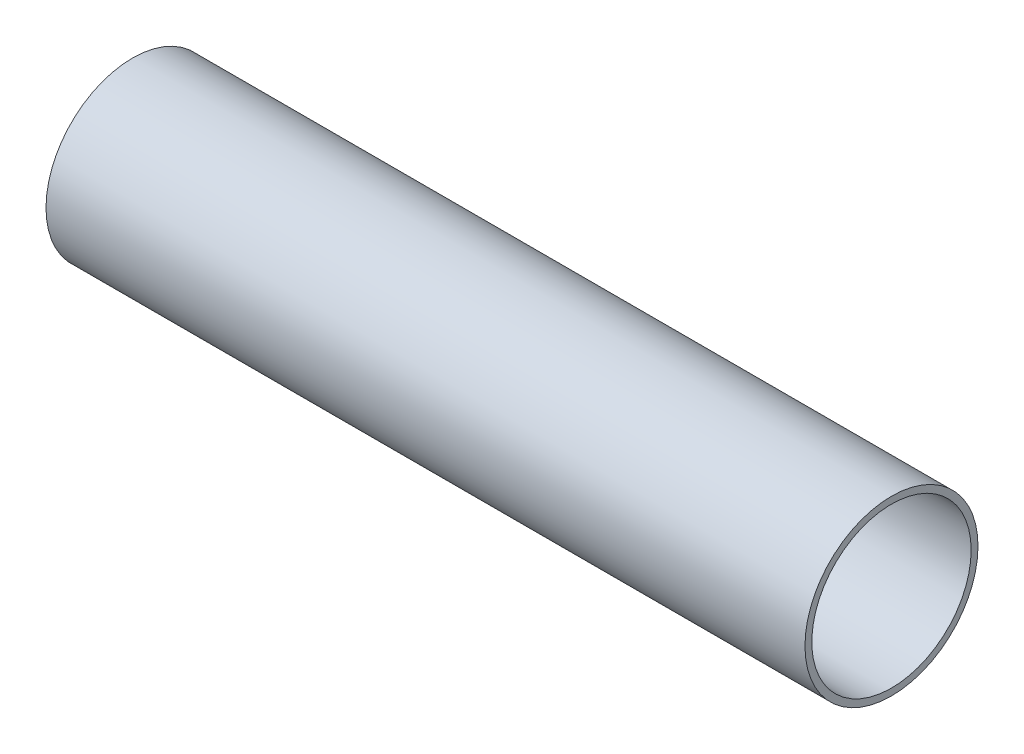
SolidWorks part; units mm, degrees
material "PVC 0.007 Plastificado"
ref_plane "Front" through (0, 0, 0) normal (0, 0, 1) x (1, 0, 0)
ref_plane "Top" through (0, 0, 0) normal (0, 1, 0) x (1, 0, 0)
ref_plane "Right" through (0, 0, 0) normal (1, 0, 0) x (0, 0, -1)
sketch "Croquis1" plane through (0, 0, 0) normal (1, 0, 0) x (0, 0, -1)
  circle A0 centre (0, 0) radius 57
  circle A1 centre (0, 0) radius 52.5
  dimension "D1" = 114
extrude "Saliente-Extruir1" add sketch "Croquis1" along normal blind 500
